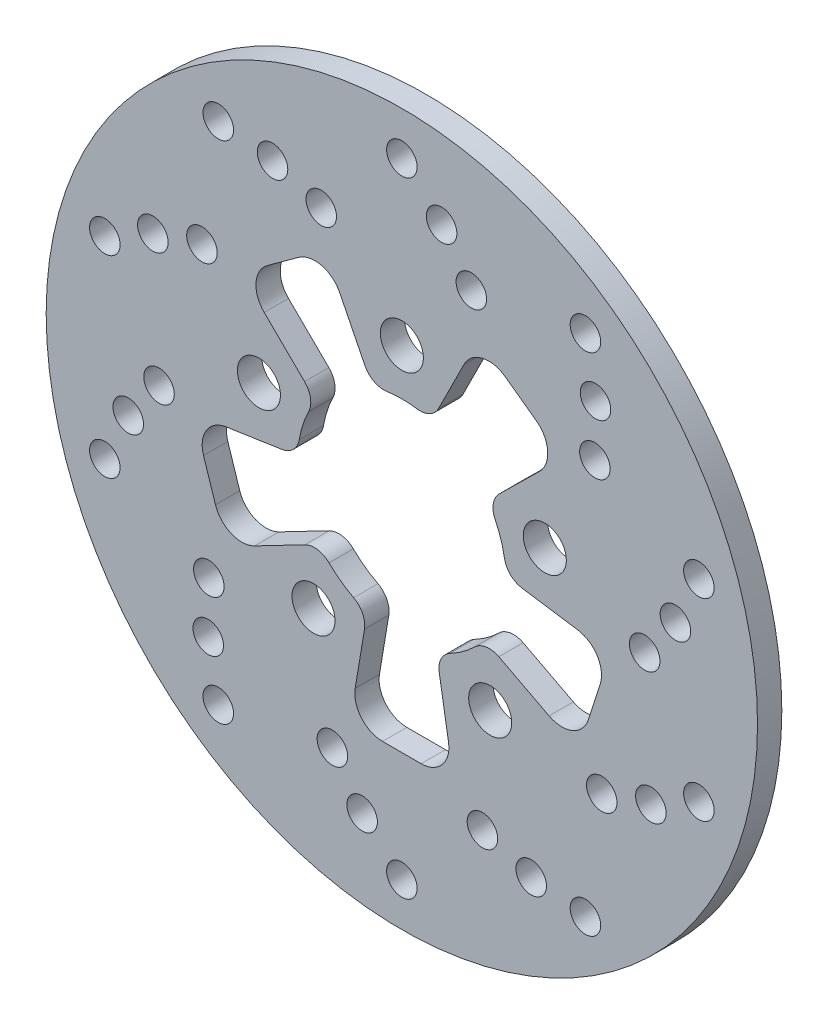
SolidWorks part; units mm, degrees
material "3003 Alloy"
ref_plane "Front Plane" through (0, 0, 0) normal (0, 0, 1) x (1, 0, 0)
ref_plane "Top Plane" through (0, 0, 0) normal (0, 1, 0) x (1, 0, 0)
ref_plane "Right Plane" through (0, 0, 0) normal (1, 0, 0) x (0, 0, -1)
ref_axis "Axis1" through (0, 0, -0.4445) along (0, 0, 1)
ref_plane "Plane1" through (0, 0, 0) normal (0.809, -0.5878, 0) x (0, 0, -1)
sketch "Sketch1" plane through (0, 0, 0) normal (0, 0, 1) x (1, 0, 0)
  circle A0 centre (0, 0) radius 130.175
  circle A1 centre (0, 0) radius 55 construction
  circle A2 centre (0, 55) radius 7.874
  circle A3 centre (52.3081, 16.9959) radius 7.874
  circle A4 centre (32.3282, -44.4959) radius 7.874
  circle A5 centre (-32.3282, -44.4959) radius 7.874
  circle A6 centre (-52.3081, 16.9959) radius 7.874
  dimension "D1" = 260.35
  dimension "D2" = 110
  dimension "D3" = 15.748
  dimension "D4" = 5
extrude "Extrude1" add sketch "Sketch1" along normal blind 8.89
sketch "Sketch3" plane through (0, 0, 0) normal (0, 0, -1) x (-1, 0, 0)
  circle A0 centre (0, 0) radius 38.1
  dimension "D1" = 76.2
extrude "Extrude3" cut sketch "Sketch3" against normal through all
sketch "Sketch4" plane through (0, 0, 8.89) normal (0, 0, 1) x (1, 0, 0)
  circle A0 centre (0, 114.3) radius 5.588
  circle A11 centre (14.5409, 100.5541) radius 5.588
  circle A12 centre (25.4314, 85.1848) radius 5.588
  circle A13 centre (70.868, 72.803) radius 5.588
  circle A14 centre (70.6448, 53.9678) radius 5.588
  circle A15 centre (67.1839, 92.4706) radius 5.588
  circle A21 centre (100.126, 17.2437) radius 5.588
  circle A22 centre (88.8743, 2.1369) radius 5.588
  circle A23 centre (108.7058, 35.3206) radius 5.588
  circle A24 centre (91.1392, -44.9021) radius 5.588
  circle A25 centre (73.1569, -50.5102) radius 5.588
  circle A26 centre (108.7058, -35.3206) radius 5.588
  circle A27 centre (47.3404, -89.8969) radius 5.588
  circle A28 centre (29.496, -83.8642) radius 5.588
  circle A29 centre (67.1839, -92.4706) radius 5.588
  circle A30 centre (-14.5409, -100.5541) radius 5.588
  circle A31 centre (-25.4314, -85.1848) radius 5.588
  circle A32 centre (0, -114.3) radius 5.588
  circle A33 centre (-70.868, -72.803) radius 5.588
  circle A34 centre (-70.6448, -53.9678) radius 5.588
  circle A35 centre (-67.1839, -92.4706) radius 5.588
  circle A36 centre (-100.126, -17.2437) radius 5.588
  circle A37 centre (-88.8743, -2.1369) radius 5.588
  circle A38 centre (-108.7058, -35.3206) radius 5.588
  circle A39 centre (-91.1392, 44.9021) radius 5.588
  circle A40 centre (-73.1569, 50.5102) radius 5.588
  circle A41 centre (-108.7058, 35.3206) radius 5.588
  circle A42 centre (-47.3404, 89.8969) radius 5.588
  circle A43 centre (-29.496, 83.8642) radius 5.588
  circle A44 centre (-67.1839, 92.4706) radius 5.588
  dimension "D2" = 11.176
  dimension "D4" = 11.176
  dimension "D5" = 11.176
  dimension "D1" = 114.3
  dimension "D6" = 101.6
  dimension "D7" = 88.9
extrude "Extrude4" cut sketch "Sketch4" against normal through all
sketch "Sketch8" plane through (0, 0, 8.89) normal (0, 0, 1) x (1, 0, 0)
  line L0 (28.0967, 71.0816) -> (58.9202, 48.687)
  line L1 (58.9202, 48.687) -> (31.3884, 21.5958)
  line L2 (28.0967, 71.0816) -> (10.8393, 36.5256)
  line L3 (43.5085, 59.8843) -> (60.4348, 83.1813) construction
  line L4 (10.8393, 36.5256) -> (31.3884, 21.5958)
  line L6 (-22.4343, -30.8782) -> (22.4343, 30.8782) construction
  circle A0 centre (0, 0) radius 38.1 construction
  dimension "D1" = 38.1
  dimension "D2" = 38.1
  dimension "D3" = 25.4
extrude "Extrude9" cut sketch "Sketch8" against normal through all
fillet "Fillet1" radius 7.62 2 edges at (31.3884, 21.5958, 4.445) (10.8393, 36.5256, 4.445)
fillet "Fillet2" radius 10.16 2 edges at (58.9202, 48.687, 4.445) (28.0967, 71.0816, 4.445)
pattern_circular "CirPattern1" count 5 over 360 about axis through (0, 0, 0) along (0, 0, -1) of "Extrude9", "Fillet1", "Fillet2"
equation "\"D4@Sketch4\" = \"D2@Sketch4\""
equation "\"D5@Sketch4\" = \"D2@Sketch4\""
